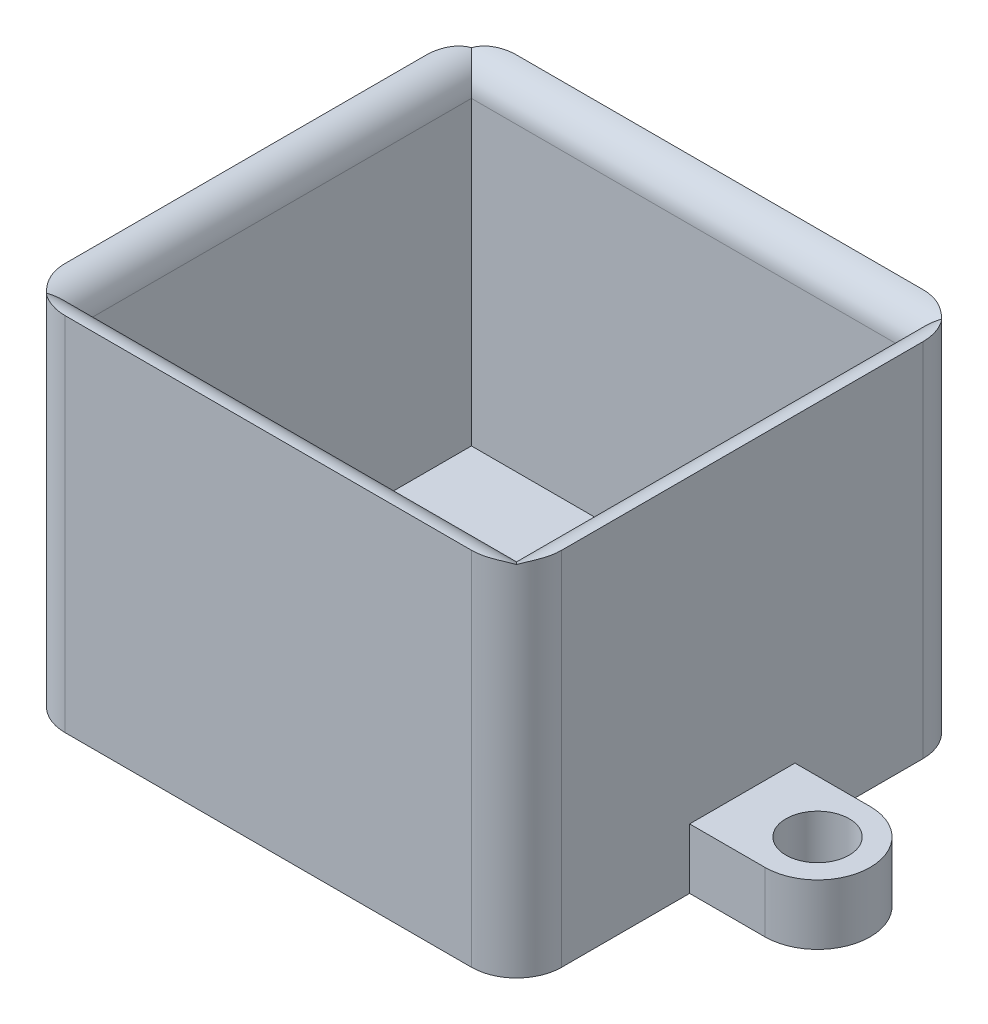
SolidWorks part; units mm, degrees
ref_plane "Front Plane" through (0, 0, 0) normal (0, 0, 1) x (1, 0, 0)
ref_plane "Top Plane" through (0, 0, 0) normal (0, 1, 0) x (1, 0, 0)
ref_plane "Right Plane" through (0, 0, 0) normal (1, 0, 0) x (0, 0, -1)
sketch "Sketch2" plane through (0, 0, 0) normal (0, 1, 0) x (1, 0, 0)
  line L1 (-14.5, 13) -> (14.5, 13)
  line L2 (-14.5, 13) -> (-14.5, -13)
  line L3 (-14.5, -13) -> (14.5, -13)
  line L4 (14.5, 13) -> (14.5, -13)
  line L5 (-14.5, 13) -> (14.5, -13) construction
  line L6 (-14.5, -13) -> (14.5, 13) construction
  line L7 (-16.5, 15) -> (16.5, 15)
  line L8 (-16.5, 15) -> (-16.5, -15)
  line L9 (-16.5, -15) -> (16.5, -15)
  line L10 (16.5, 15) -> (16.5, -15)
  line L11 (-16.5, 15) -> (16.5, -15) construction
  line L12 (-16.5, -15) -> (16.5, 15) construction
  point P0 (0, 0)
  point P6 (0, 0)
  dimension "D1" = 29
  dimension "D2" = 26
  dimension "D3" = 2
  dimension "D4" = 2
extrude "Boss-Extrude1" add sketch "Sketch2" along normal blind 22
sketch "Sketch3" plane through (0, 0, 0) normal (0, -1, 0) x (1, 0, 0)
  line L1 (-16.5, 15) -> (16.5, 15)
  line L2 (-16.5, 15) -> (-16.5, -15)
  line L3 (-16.5, -15) -> (16.5, -15)
  line L4 (16.5, 15) -> (16.5, -15)
extrude "Boss-Extrude2" add sketch "Sketch3" along normal blind 2
sketch "Sketch4" plane through (0, -2, 0) normal (0, -1, 0) x (1, 0, 0)
  line L0 (0, 15) -> (0, -15) construction
  line L1 (16.5, 15) -> (-16.5, 15) construction
  line L2 (-16.5, -15) -> (16.5, -15) construction
  line L3 (-21.5, 3.5) -> (-16.5, 3.5)
  line L4 (-16.5, 15) -> (-16.5, -15) construction
  line L5 (-21.5, -3.5) -> (-16.5, -3.5)
  line L6 (-16.5, 3.5) -> (-16.5, -3.5)
  line L7 (0, 0) -> (-16.5, 0) construction
  line L8 (16.5, 3.5) -> (16.5, -3.5)
  line L9 (21.5, -3.5) -> (16.5, -3.5)
  line L10 (21.5, 3.5) -> (16.5, 3.5)
  arc A0 (-21.5, 3.5) -> (-21.5, -3.5) centre (-21.5, 0) ccw
  circle A1 centre (-21.5, 0) radius 2.1
  circle A2 centre (21.5, 0) radius 2.1
  arc A3 (21.5, 3.5) -> (21.5, -3.5) centre (21.5, 0) cw
  dimension "D1" = 3.5
  dimension "D2" = 4.2
  dimension "D3" = 5
extrude "Boss-Extrude3" add sketch "Sketch4" against normal blind 4
fillet "Fillet1" radius 3 4 edges at (16.5, 10, -15) (-16.5, 10, -15) (16.5, 10, 15) (-16.5, 10, 15)
fillet "Fillet2" radius 2 4 edges at (14.5, 22, 0) (0, 22, -13) (-14.5, 22, 0) (0, 22, 13)
